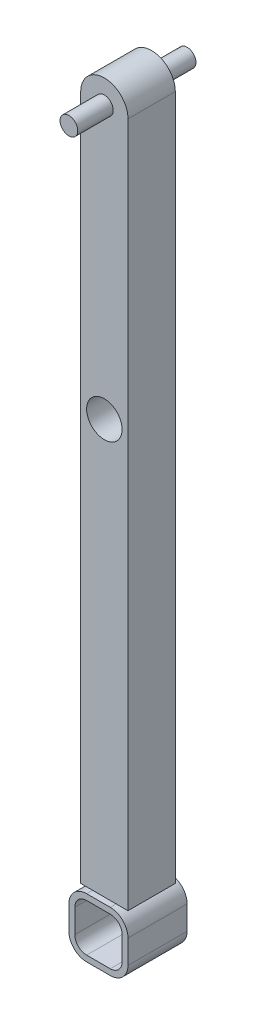
SolidWorks part; units mm, degrees
ref_plane "前视基准面" through (0, 0, 0) normal (0, 0, 1) x (1, 0, 0)
ref_plane "上视基准面" through (0, 0, 0) normal (0, 1, 0) x (1, 0, 0)
ref_plane "右视基准面" through (0, 0, 0) normal (1, 0, 0) x (0, 0, -1)
sketch "草图1" plane through (0, 0, 0) normal (0, 0, 1) x (1, 0, 0)
  line L0 (-10, 25) -> (10, 25)
  line L1 (-10, 20) -> (10, 20)
  line L2 (-20, 10) -> (-20, -10)
  line L3 (-10, -20) -> (10, -20)
  line L4 (20, 10) -> (20, -10)
  line L5 (-20, 20) -> (20, -20) construction
  line L6 (-20, -20) -> (20, 20) construction
  line L7 (25, 10) -> (25, -10)
  line L8 (-10, -25) -> (10, -25)
  line L9 (-25, 10) -> (-25, -10)
  arc A0 (-20, -10) -> (-10, -20) centre (-10, -10) ccw
  arc A1 (10, -20) -> (20, -10) centre (10, -10) ccw
  arc A2 (10, 20) -> (20, 10) centre (10, 10) cw
  arc A3 (-10, 20) -> (-20, 10) centre (-10, 10) ccw
  arc A4 (10, 25) -> (25, 10) centre (10, 10) cw
  arc A5 (10, -25) -> (25, -10) centre (10, -10) ccw
  arc A6 (-25, -10) -> (-10, -25) centre (-10, -10) ccw
  arc A7 (-10, 25) -> (-25, 10) centre (-10, 10) ccw
  point P0 (0, 0)
  dimension "D1" = 40
  dimension "D2" = 40
  dimension "D3" = 10
  dimension "D4" = 5
extrude "凸台-拉伸1" add sketch "草图1" along normal blind 50
sketch "草图2" plane through (0, 25, 0) normal (0, 1, 0) x (1, 0, 0)
  line L1 (-20, -5) -> (20, -5)
  line L2 (-20, -5) -> (-20, -45)
  line L3 (-20, -45) -> (20, -45)
  line L4 (20, -5) -> (20, -45)
  line L5 (-20, -5) -> (20, -45) construction
  line L6 (-20, -45) -> (20, -5) construction
  point P0 (0, -25)
  dimension "D1" = 25
  dimension "D2" = 40
  dimension "D3" = 40
extrude "凸台-拉伸2" add sketch "草图2" along normal blind 600
fillet "圆角1" 2 edges at (20, 625, 25) (-20, 625, 25) type full round first side face at (20, 325, 25) second side face at (-20, 325, 25) middle face at (0, 625, 25)
sketch "草图5" plane through (0, 0, 45) normal (0, 0, 1) x (1, 0, 0)
  circle A0 centre (0, 605) radius 7.5
  dimension "D1" = 15
extrude "凸台-拉伸4" add sketch "草图5" along normal blind 30
ref_plane "基准面2" through (0, 0, 25) normal (0, 0, 1) x (1, 0, 0)
mirror "镜向2" about plane through (0, 0, 25) normal (0, 0, 1) of "凸台-拉伸4"
sketch "草图6" plane through (25, 0, 45) normal (0, 0, 1) x (1, 0, 0)
  circle A0 centre (-25, 375) radius 15
  point P4 (0, 0)
  point P8 (-25, 625)
  dimension "D1" = 30
extrude "切除-拉伸1" cut sketch "草图6" against normal through all
